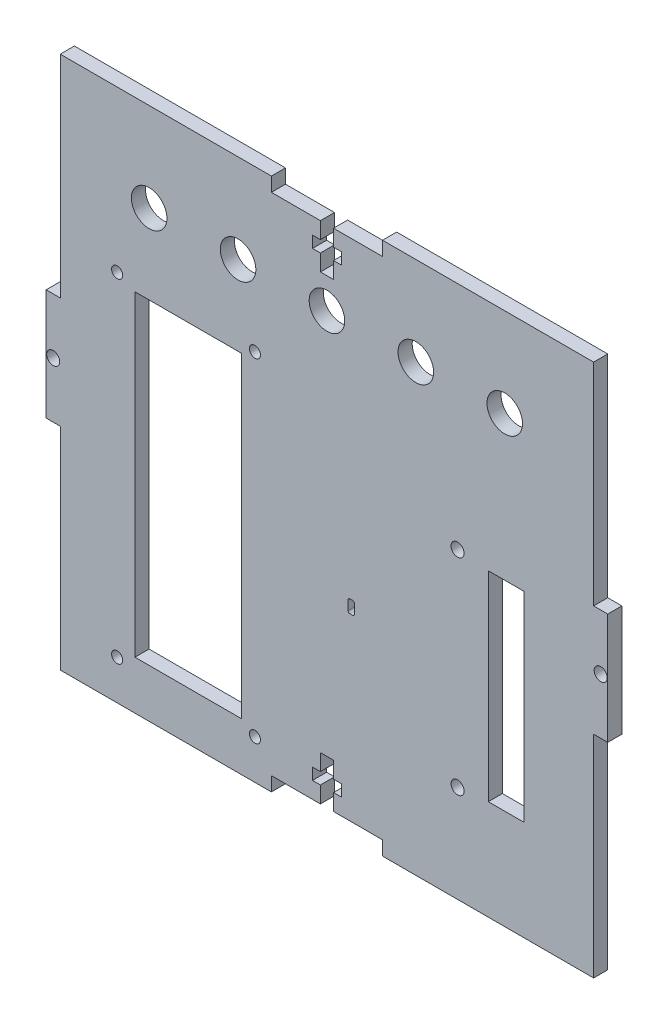
SolidWorks part; units mm, degrees
ref_plane "Front Plane" through (0, 0, 0) normal (0, 0, 1) x (1, 0, 0)
ref_plane "Top Plane" through (0, 0, 0) normal (0, 1, 0) x (1, 0, 0)
ref_plane "Right Plane" through (0, 0, 0) normal (1, 0, 0) x (0, 0, -1)
sketch "Sketch1" plane through (0, 0, 0) normal (0, 0, 1) x (1, 0, 0)
  line L0 (0, 60) -> (0, -60) construction
  line L1 (-60, 60) -> (60, 60)
  line L2 (-60, 60) -> (-60, -60)
  line L3 (-60, -60) -> (60, -60)
  line L4 (60, 60) -> (60, -60)
  line L5 (-60, 60) -> (60, -60) construction
  line L6 (-60, -60) -> (60, 60) construction
  line L7 (-60, 0) -> (60, 0) construction
  line L8 (-3.25, -50.525) -> (3.25, -50.525)
  line L9 (12.5, 60) -> (-12.5, 60)
  line L10 (12.5, 60) -> (12.5, 56.825)
  line L11 (12.5, 56.825) -> (-12.5, 56.825)
  line L12 (-12.5, 60) -> (-12.5, 56.825)
  line L13 (12.5, 60) -> (-12.5, 56.825) construction
  line L14 (12.5, 56.825) -> (-12.5, 60) construction
  line L15 (-1.47, 56.825) -> (1.47, 56.825)
  line L16 (-1.47, 56.825) -> (-1.47, 46.825)
  line L17 (-1.47, 46.825) -> (1.47, 46.825)
  line L18 (1.47, 56.825) -> (1.47, 46.825)
  line L19 (-1.47, 56.825) -> (1.47, 46.825) construction
  line L20 (-1.47, 46.825) -> (1.47, 56.825) construction
  line L21 (-3.25, 53.125) -> (3.25, 53.125)
  line L22 (-3.25, 53.125) -> (-3.25, 50.525)
  line L23 (-3.25, 50.525) -> (3.25, 50.525)
  line L24 (3.25, 53.125) -> (3.25, 50.525)
  line L25 (-3.25, 53.125) -> (3.25, 50.525) construction
  line L26 (-3.25, 50.525) -> (3.25, 53.125) construction
  line L27 (3.25, -53.125) -> (3.25, -50.525)
  line L28 (-3.25, -53.125) -> (3.25, -53.125)
  line L29 (-3.25, -53.125) -> (-3.25, -50.525)
  line L30 (-1.47, -46.825) -> (1.47, -46.825)
  line L31 (1.47, -56.825) -> (1.47, -46.825)
  line L32 (-1.47, -56.825) -> (1.47, -56.825)
  line L33 (-1.47, -56.825) -> (-1.47, -46.825)
  line L34 (12.5, -56.825) -> (-12.5, -56.825)
  line L35 (-12.5, -60) -> (-12.5, -56.825)
  line L36 (12.5, -60) -> (-12.5, -60)
  line L37 (12.5, -60) -> (12.5, -56.825)
  line L38 (63.175, -12.5) -> (60, -12.5)
  line L39 (-63.175, 12.5) -> (-60, 12.5)
  line L40 (-63.175, 12.5) -> (-63.175, -12.5)
  line L41 (-63.175, -12.5) -> (-60, -12.5)
  line L42 (-60, 12.5) -> (-60, -12.5)
  line L43 (-63.175, 12.5) -> (-60, -12.5) construction
  line L44 (-63.175, -12.5) -> (-60, 12.5) construction
  line L45 (60, 12.5) -> (60, -12.5)
  line L46 (63.175, 12.5) -> (60, 12.5)
  line L47 (63.175, 12.5) -> (63.175, -12.5)
  circle A0 centre (-61.5875, 0) radius 1.47
  circle A1 centre (61.5875, 0) radius 1.47
  point P0 (0, 0)
  point P10 (0, 58.4125)
  point P15 (0, 51.825)
  point P20 (0, 51.825)
  point P37 (-61.5875, 0)
  dimension "D11" = 2.94
  dimension "D1" = 120
  dimension "D2" = 120
  dimension "D3" = 3.175
  dimension "D4" = 10
  dimension "D5" = 2.94
  dimension "D6" = 25
  dimension "D7" = 6.5
  dimension "D8" = 2.6
  dimension "D9" = 6.3
  dimension "D10" = 3.175
extrude "Boss-Extrude1" add sketch "Sketch1" along normal mid plane 3.175 contours L21 L24 L23 L18 L17 L16 L22 L11 L12 L1 L2 L3 L4 L10 | L40 L39 L42 L41 | A0 | L38 L45 L46 L47 | A1 region at (0, 0, 0)
sketch "Sketch3" plane through (0, 0, -1.5875) normal (0, 0, -1) x (-1, 0, 0)
  line L0 (-9.6476, 0) -> (-9.6476, -15) construction
  line L5 (-9.6476, -15) -> (-19.2951, -15) construction
  line L6 (-40.3, 7.5) -> (-40.3, -22.5) construction
  line L7 (-36.3, 7.5) -> (-44.3, 7.5)
  line L8 (-36.3, 7.5) -> (-36.3, -37.5)
  line L9 (-36.3, -37.5) -> (-44.3, -37.5)
  line L10 (-44.3, 7.5) -> (-44.3, -37.5)
  line L11 (-38.7125, -40) -> (-38.7125, 10) construction
  line L12 (-41.8875, 10) -> (-41.8875, -40) construction
  line L13 (0, 0) -> (-19.2951, 0) construction
  dimension "D1" = 8
  dimension "D2" = 45
  dimension "D3" = 15
extrude "Cut-Extrude1" cut sketch "Sketch3" against normal through all
sketch "Sketch4" plane through (0, 0, -1.5875) normal (0, 0, -1) x (-1, 0, 0)
  line L0 (43.2, 21.2555) -> (43.2, -48.2445) construction
  line L1 (43.2, 22.1055) -> (19.2, 22.1055)
  line L2 (43.2, 22.1055) -> (43.2, -49.0945)
  line L3 (43.2, -49.0945) -> (19.2, -49.0945)
  line L4 (19.2, 22.1055) -> (19.2, -49.0945)
  line L5 (19.2, -48.2445) -> (19.2, 21.2555) construction
  line L6 (20.05, 22.1055) -> (26.7, 22.1055) construction
  line L7 (42.35, -49.0945) -> (20.05, -49.0945) construction
extrude "Cut-Extrude2" cut sketch "Sketch4" against normal through all
sketch "Sketch5" plane through (0, 0, -1.5875) normal (0, 0, -1) x (-1, 0, 0)
  line L0 (-5.1534, -16.25) -> (-5.7792, -16.25) construction
  line L1 (-5.7792, -13.75) -> (-5.1534, -13.75) construction
  line L2 (-4.9534, -13.95) -> (-4.9534, -16.05) construction
  line L3 (-5.1534, -16.25) -> (-5.7792, -16.25)
  line L4 (-5.7792, -13.75) -> (-5.1534, -13.75)
  line L5 (-4.9534, -13.95) -> (-4.9534, -16.05)
  line L6 (-5.1534, -16.45) -> (-5.7792, -16.45)
  line L7 (-5.7792, -13.55) -> (-5.1534, -13.55)
  line L8 (-4.7534, -13.95) -> (-4.7534, -16.05)
  arc A0 (-5.1534, -16.25) -> (-4.9534, -16.05) centre (-5.1534, -16.05) ccw construction
  arc A1 (-5.9775, -16.0753) -> (-5.7792, -16.25) centre (-5.7792, -16.05) ccw construction
  arc A2 (-5.9775, -13.9247) -> (-5.9775, -16.0753) centre (2.4542, -15) ccw construction
  arc A3 (-5.7792, -13.75) -> (-5.9775, -13.9247) centre (-5.7792, -13.95) ccw construction
  arc A4 (-4.9534, -13.95) -> (-5.1534, -13.75) centre (-5.1534, -13.95) ccw construction
  arc A5 (-5.1534, -16.25) -> (-4.9534, -16.05) centre (-5.1534, -16.05) ccw
  arc A6 (-5.9775, -16.0753) -> (-5.7792, -16.25) centre (-5.7792, -16.05) ccw
  arc A7 (-5.9775, -13.9247) -> (-5.9775, -16.0753) centre (2.4542, -15) ccw
  arc A8 (-5.7792, -13.75) -> (-5.9775, -13.9247) centre (-5.7792, -13.95) ccw
  arc A9 (-4.9534, -13.95) -> (-5.1534, -13.75) centre (-5.1534, -13.95) ccw
  arc A10 (-6.1759, -16.1006) -> (-5.7792, -16.45) centre (-5.7792, -16.05) ccw
  arc A11 (-6.1759, -13.8994) -> (-6.1759, -16.1006) centre (2.4542, -15) ccw
  arc A12 (-5.7792, -13.55) -> (-6.1759, -13.8994) centre (-5.7792, -13.95) ccw
  arc A13 (-4.7534, -13.95) -> (-5.1534, -13.55) centre (-5.1534, -13.95) ccw
  arc A14 (-5.1534, -16.45) -> (-4.7534, -16.05) centre (-5.1534, -16.05) ccw
  dimension "D1" = 0.2
extrude "Cut-Extrude4" cut sketch "Sketch5" against normal through all contours L8 A14 L6 A10 A11 A12 L7 A13
sketch "Sketch6" plane through (0, 0, -1.5875) normal (0, 0, -1) x (-1, 0, 0)
  line L0 (-60, 40) -> (60, 40) construction
  line L1 (-60, 60) -> (-60, 12.5) construction
  line L2 (60, 60) -> (60, 12.5) construction
  line L3 (60, 60) -> (12.5, 60) construction
  line L4 (-40, 40) -> (-20, 40)
  line L5 (-20, 40) -> (0, 40)
  line L6 (0, 40) -> (20, 40)
  line L7 (20, 40) -> (40, 40)
  line L8 (-60, 60) -> (-60, 12.5) construction
  line L9 (0, 40) -> (20, 40)
  line L10 (-20, 40) -> (0, 40)
  line L11 (-40, 40) -> (-20, 40)
  line L12 (-60, 40) -> (-40, 40)
  circle A0 centre (40, 40) radius 4
  circle A1 centre (20, 40) radius 4
  circle A2 centre (0, 40) radius 4
  circle A3 centre (-20, 40) radius 4
  circle A4 centre (-40, 40) radius 4
  dimension "D4" = 8
  dimension "D1" = 20
  dimension "D2" = 20
  dimension "D3" = 20
  dimension "D5" = 5
extrude "Cut-Extrude5" cut sketch "Sketch6" against normal through all contours A0 | A1 | A2 | A3 | A4
sketch "Sketch9" plane through (0, 0, 1.5875) normal (0, 0, 1) x (1, 0, 0)
  circle A0 centre (-47.2, 23.9055) radius 1.25 construction
  circle A1 centre (-16.2, 23.9055) radius 1.25 construction
  circle A2 centre (-16.2, -51.0945) radius 1.25 construction
  circle A3 centre (-47.2, -51.0945) radius 1.25 construction
  circle A4 centre (-47.2, 23.9055) radius 1.25
  circle A5 centre (-16.2, 23.9055) radius 1.25
  circle A6 centre (-16.2, -51.0945) radius 1.25
  circle A7 centre (-47.2, -51.0945) radius 1.25
  circle A8 centre (29.3875, 8.1613) radius 1.47 construction
  circle A9 centre (29.3875, -38.1613) radius 1.47 construction
  circle A10 centre (29.3875, 8.1613) radius 1.47
  circle A11 centre (29.3875, -38.1613) radius 1.47
extrude "Cut-Extrude6" cut sketch "Sketch9" against normal through all
